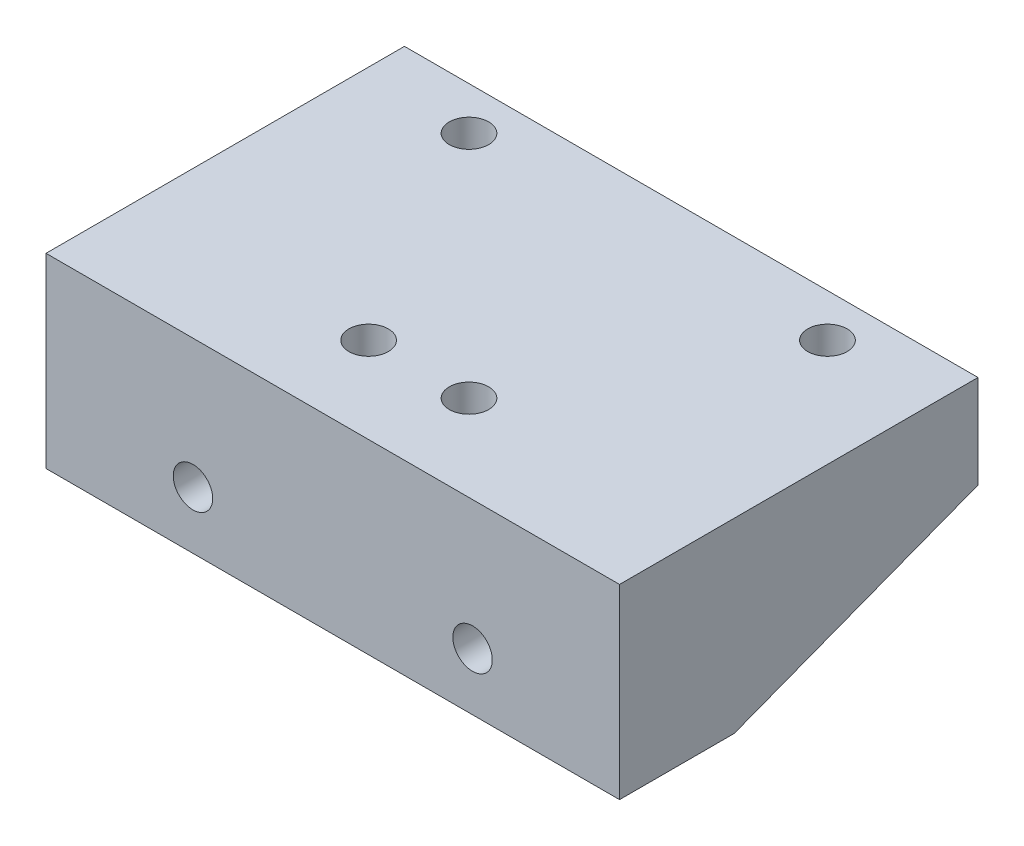
SolidWorks part; units mm, degrees
material "6061-T6 (SS)"
ref_plane "Front Plane" through (0, 0, 0) normal (0, 0, 1) x (1, 0, 0)
ref_plane "Top Plane" through (0, 0, 0) normal (0, 1, 0) x (1, 0, 0)
ref_plane "Right Plane" through (0, 0, 0) normal (1, 0, 0) x (0, 0, -1)
sketch "Sketch1" plane through (0, 0, 0) normal (0, 0, 1) x (1, 0, 0)
  line L1 (0, 0) -> (62, 0)
  line L2 (0, 0) -> (0, 26)
  line L3 (0, 26) -> (62, 26)
  line L4 (62, 0) -> (62, 26)
  dimension "D1" = 62
  dimension "D2" = 26
extrude "Boss-Extrude1" add sketch "Sketch1" along normal blind 6
sketch "Sketch2" plane through (0, 0, 6) normal (0, 0, 1) x (1, 0, 0)
  line L0 (62, 26) -> (0, 26) construction
  line L1 (-9, 26) -> (71, 26)
  line L2 (-9, 26) -> (-9, 16)
  line L3 (-9, 16) -> (71, 16)
  line L4 (71, 26) -> (71, 16)
  line L5 (31, 0) -> (31, 16) construction
  line L6 (0, 0) -> (62, 0) construction
  dimension "D1" = 10
  dimension "D2" = 80
extrude "Boss-Extrude2" add sketch "Sketch2" against normal blind 50
sketch "Sketch3" plane through (0, 0, 0) normal (0, 0, -1) x (-1, 0, 0)
  line L0 (-62, 0) -> (-62, 16) construction
  line L1 (0, 16) -> (0, 0) construction
  point P0 (-50.5, 8)
  point P2 (-11.5, 8)
  dimension "D1" = 11.5
  dimension "D2" = 11.5
hole_wizard "M5 Clearance Hole1" positions "Sketch3" profile "Sketch4" hole size "M5" standard "DIN"
sketch "Sketch4" plane through (50.5, 8, 0) normal (1, 0, 0) x (0, 1, 0)
  line L0 (0, 0) -> (0, 11.6524)
  line L1 (0, 11.6524) -> (2.75, 10)
  line L2 (2.75, 10) -> (2.75, 0)
  line L5 (2.75, 0) -> (0, 0)
  line L10 (0, 11.6524) -> (-2.75, 10) construction
  line L11 (0, -6.35) -> (0, 107.95) construction
  dimension "Hole Dia." = 5.5
  dimension "Hole Depth" = 10
  dimension "Drill Angle" = 118
sketch "Sketch5" plane through (71, 0, 0) normal (1, 0, 0) x (0, 0, -1)
  line L0 (-6, 0) -> (10, 0)
  line L2 (44, 16) -> (-6, 16)
  line L3 (-6, 16) -> (-6, 0)
  line L4 (44, 16) -> (44, 13)
  line L5 (44, 13) -> (10, 0)
  dimension "D1" = 16
  dimension "D2" = 3
extrude "Boss-Extrude3" add sketch "Sketch5" against normal up to surface (9 mm away) up to face at (62, 8, 3)
extrude "Boss-Extrude4" add sketch "Sketch5<2>" along normal up to surface (-71 mm away) from surface up to face at (0, 8, 3) starting at face at (-9, 21, -19)
sketch "Sketch5<2>" plane through (71, 0, 0) normal (1, 0, 0) x (0, 0, -1) same geometry as "Sketch5"
sketch "Sketch6" plane through (0, 16, 0) normal (0, -1, 0) x (-1, 0, 0)
  line L1 (0, 0) -> (0, 44) construction
  line L2 (-56, 38) -> (-6, 38) construction
  line L4 (0, 44) -> (-62, 44) construction
  line L5 (-24, 6) -> (-38, 6) construction
  line L7 (-31, 6) -> (-31, 0) construction
  line L8 (-62, 0) -> (0, 0) construction
  line L9 (-62, 10) -> (-62, 44) construction
  point P0 (-38, 6)
  point P2 (-24, 6)
  point P4 (-56, 38)
  point P6 (-6, 38)
  dimension "D2" = 6
  dimension "D3" = 6
  dimension "D4" = 14
  dimension "D5" = 6
  dimension "D1" = 6
hole_wizard "M5 Clearance Hole2" positions "Sketch6" profile "Sketch7" hole size "M5" standard "DIN"
sketch "Sketch7" plane through (38, 16, -6) normal (1, 0, 0) x (0, 0, -1)
  line L0 (0, 0) -> (0, 11.6524)
  line L1 (0, 11.6524) -> (2.75, 10)
  line L2 (2.75, 10) -> (2.75, 0)
  line L5 (2.75, 0) -> (0, 0)
  line L10 (0, 11.6524) -> (-2.75, 10) construction
  line L11 (0, -6.35) -> (0, 107.95) construction
  dimension "Hole Dia." = 5.5
  dimension "Hole Depth" = 10
  dimension "Drill Angle" = 118
fillet "Fillet1" radius 3.5 2 edges at (62, 8, 0) (0, 8, 0)
fillet "Fillet2" radius 1 5 edges at (62, 16, -23.75) (60.9749, 16, -1.0251) (31, 16, 0) (1.0251, 16, -1.0251) (0, 16, -23.75)
equation "\"D2@Sketch3\"=\"D1@Sketch3\""
equation "\"D2@Sketch6\"=\"D1@Sketch6\""
